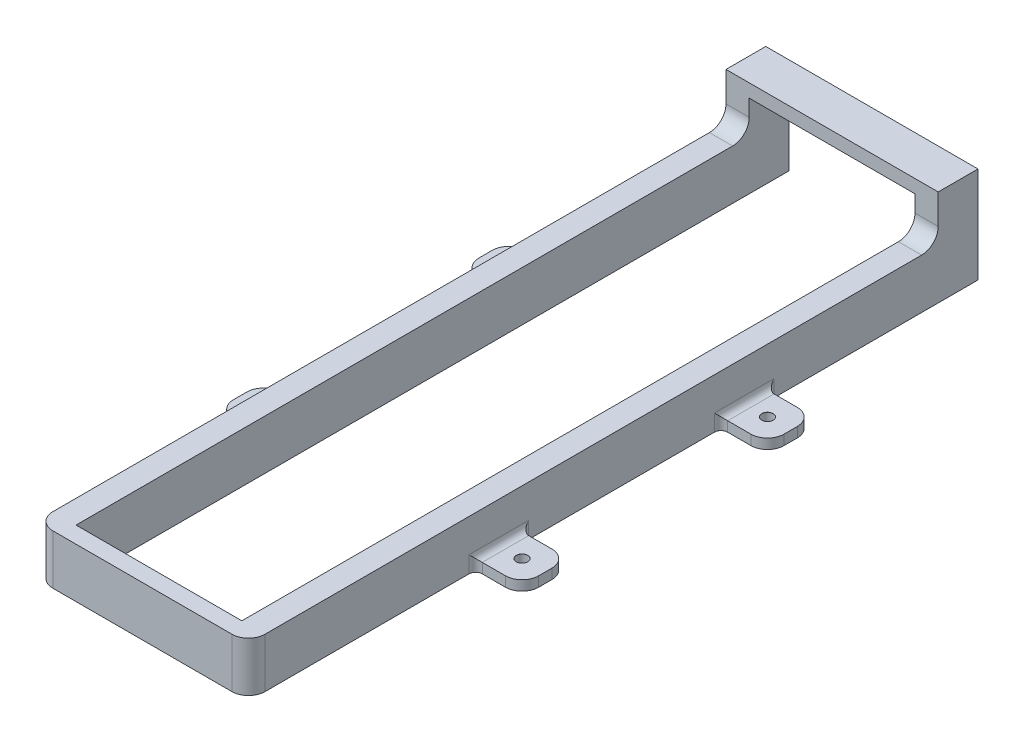
SolidWorks part; units mm, degrees
ref_plane "Front Plane" through (0, 0, 0) normal (0, 0, 1) x (1, 0, 0)
ref_plane "Top Plane" through (0, 0, 0) normal (0, 1, 0) x (1, 0, 0)
ref_plane "Right Plane" through (0, 0, 0) normal (1, 0, 0) x (0, 0, -1)
sketch "Sketch1" plane through (0, 0, 0) normal (0, 1, 0) x (1, 0, 0)
  line L0 (25, 107.5) -> (35, 107.5)
  line L2 (-25, 107.5) -> (-25, -107.5)
  line L3 (-25, -107.5) -> (25, -107.5)
  line L4 (25, 107.5) -> (25, -107.5)
  line L5 (-25, 107.5) -> (25, -107.5) construction
  line L6 (-25, -107.5) -> (25, 107.5) construction
  line L7 (35, 107.5) -> (35, -117.5)
  line L8 (35, -117.5) -> (-35, -117.5)
  line L9 (-35, -117.5) -> (-35, 107.5)
  line L10 (-35, 107.5) -> (-25, 107.5)
  point P0 (0, 0)
  dimension "D1" = 50
  dimension "D2" = 215
  dimension "D3" = 50
  dimension "D4" = 10
  dimension "D5" = 10
  dimension "D6" = 10
extrude "Boss-Extrude1" add sketch "Sketch1" along normal mid plane 15
sketch "Sketch2" plane through (0, 0, -107.5) normal (0, 0, -1) x (-1, 0, 0)
  line L1 (-35, 7.5) -> (-25, 7.5)
  line L2 (-35, 7.5) -> (-35, 17.5)
  line L3 (-35, 17.5) -> (-25, 17.5)
  line L4 (-25, 7.5) -> (-25, 17.5)
  line L5 (25, 7.5) -> (35, 7.5)
  line L6 (25, 7.5) -> (25, 17.5)
  line L7 (25, 17.5) -> (35, 17.5)
  line L8 (35, 7.5) -> (35, 17.5)
  line L9 (-35, 17.5) -> (35, 17.5)
  line L10 (-35, 17.5) -> (-35, 21.5)
  line L11 (-35, 21.5) -> (35, 21.5)
  line L12 (35, 17.5) -> (35, 21.5)
  line M7 (-25, 7.5) -> (-35, 7.5)
  dimension "D1" = 10
  dimension "D2" = 4
  dimension "D3" = 70
  dimension "D4" = 10
extrude "Boss-Extrude2" add sketch "Sketch2" against normal blind 12 contours L4 L3 L2 M7 | L7 L12 L11 L10 L3 L9 | L5 L8 L7 L6 region at (30, 12.5, -107.5) region at (0, 19.5, -107.5) region at (-30, 12.5, -107.5)
sketch "Sketch3" plane through (0, 7.5, 0) normal (0, 1, 0) x (1, 0, 0)
  line L0 (35, -117.5) -> (35, 95.5) construction
  line L1 (-35, -117.5) -> (35, -117.5)
  line L2 (-35, -117.5) -> (-35, -112.5)
  line L3 (-32, -112.5) -> (32, -112.5)
  line L4 (35, -117.5) -> (35, -112.5)
  line L6 (-35, 107.5) -> (-32, 107.5)
  line L7 (-35, 107.5) -> (-35, -112.5)
  line L9 (-32, 107.5) -> (-32, -112.5)
  line L10 (35, 107.5) -> (32, 107.5)
  line L11 (35, 107.5) -> (35, -112.5)
  line L13 (32, 107.5) -> (32, -112.5)
  dimension "D1" = 5
  dimension "D2" = 3
  dimension "D3" = 3
extrude "Cut-Extrude1" cut sketch "Sketch3" against normal through all both and the other way through all
sketch "Sketch4" plane through (0, 7.5, 0) normal (0, 1, 0) x (1, 0, 0)
  line L0 (-32, -112.5) -> (-32, 95.5) construction
  line L1 (-32, 44) -> (-46, 44)
  line L2 (-32, 44) -> (-32, 30)
  line L3 (-32, 30) -> (-46, 30)
  line L4 (-46, 44) -> (-46, 30)
  line L10 (0, 0) -> (0, 40.3812) construction
  line L11 (46, -30) -> (46, -44)
  line L12 (-32, -30) -> (-46, -30)
  line L13 (-32, -30) -> (-32, -44)
  line L14 (-32, -44) -> (-46, -44)
  line L15 (-46, -30) -> (-46, -44)
  line L16 (32, -44) -> (46, -44)
  line L17 (32, -30) -> (32, -44)
  line L18 (32, -30) -> (46, -30)
  line L19 (46, 44) -> (46, 30)
  line L20 (32, 30) -> (46, 30)
  line L21 (32, 44) -> (32, 30)
  line L22 (32, 44) -> (46, 44)
  dimension "D1" = 14
  dimension "D2" = 14
  dimension "D3" = 14
  dimension "D4" = 14
  dimension "D5" = 30
  dimension "D6" = 30
extrude "Boss-Extrude3" add sketch "Sketch4" against normal up to surface (15 mm away) up to face at (0, -7.5, 1.25)
sketch "Sketch7" plane through (0, 7.5, 0) normal (0, 1, 0) x (1, 0, 0)
  line L1 (-46, 44) -> (-32, 44)
  line L2 (-46, 44) -> (-46, 30)
  line L3 (-46, 30) -> (-32, 30)
  line L4 (-32, 44) -> (-32, 30)
  line L5 (32, 44) -> (46, 44)
  line L6 (32, 44) -> (32, 30)
  line L7 (32, 30) -> (46, 30)
  line L8 (46, 44) -> (46, 30)
  line L9 (32, -30) -> (46, -30)
  line L10 (32, -30) -> (32, -44)
  line L11 (32, -44) -> (46, -44)
  line L12 (46, -30) -> (46, -44)
  line L13 (-46, -30) -> (-32, -30)
  line L14 (-46, -30) -> (-46, -44)
  line L15 (-46, -44) -> (-32, -44)
  line L16 (-32, -30) -> (-32, -44)
extrude "Cut-Extrude2" cut sketch "Sketch7" against normal blind 12
hole_wizard "M3 Clearance Hole1" positions "Sketch8" profile "Sketch9" hole size "M3" standard "ANSI Metric" end condition through all
sketch "Sketch8" plane through (0, -4.5, 0) normal (0, 1, 0) x (1, 0, 0)
  line L0 (-46, 44) -> (-46, 30) construction
  line L1 (-46, 30) -> (-32, 30) construction
  point P0 (-39, 37)
  point P2 (39, 37)
  point P4 (39, -37)
  point P6 (-39, -37)
  dimension "D1" = 7
  dimension "D2" = 85
  dimension "D3" = 7
  dimension "D4" = 67
sketch "Sketch9" plane through (-39, -4.5, -37) normal (1, 0, 0) x (0, 0, 1)
  line L0 (0, 0) -> (0, 3)
  line L1 (0, 3) -> (1.7, 3)
  line L2 (1.7, 3) -> (1.7, 0.025)
  line L3 (1.7, 0.025) -> (1.725, 0)
  line L5 (1.725, 0) -> (0, 0)
  line L6 (-1.7, 0.025) -> (-1.725, 0) construction
  line L11 (0, -6.35) -> (0, 107.95) construction
  dimension "Thru Hole Dia." = 3.4
  dimension "Thru Hole Depth" = 3
  dimension "Near C'Sink Dia." = 3.45
  dimension "Near C'Sink Angle" = 90
fillet "Fillet1" radius 2 12 edges at (-32, -6, -44) (-32, -4.5, -37) (-32, -6, -30) (-32, -6, 30) (-32, -4.5, 37) (-32, -6, 44) (32, -6, 44) (32, -4.5, 37) (32, -6, 30) (32, -6, -44) (32, -6, -30) (32, -4.5, -37)
fillet "Fillet2" radius 5 12 edges at (-46, -6, -30) (-46, -6, -44) (-46, -6, 30) (-46, -6, 44) (46, -6, -44) (46, -6, -30) (46, -6, 30) (46, -6, 44) (-32, 0, 112.5) (32, 0, 112.5) (-28.5, 7.5, -95.5) (28.5, 7.5, -95.5)
